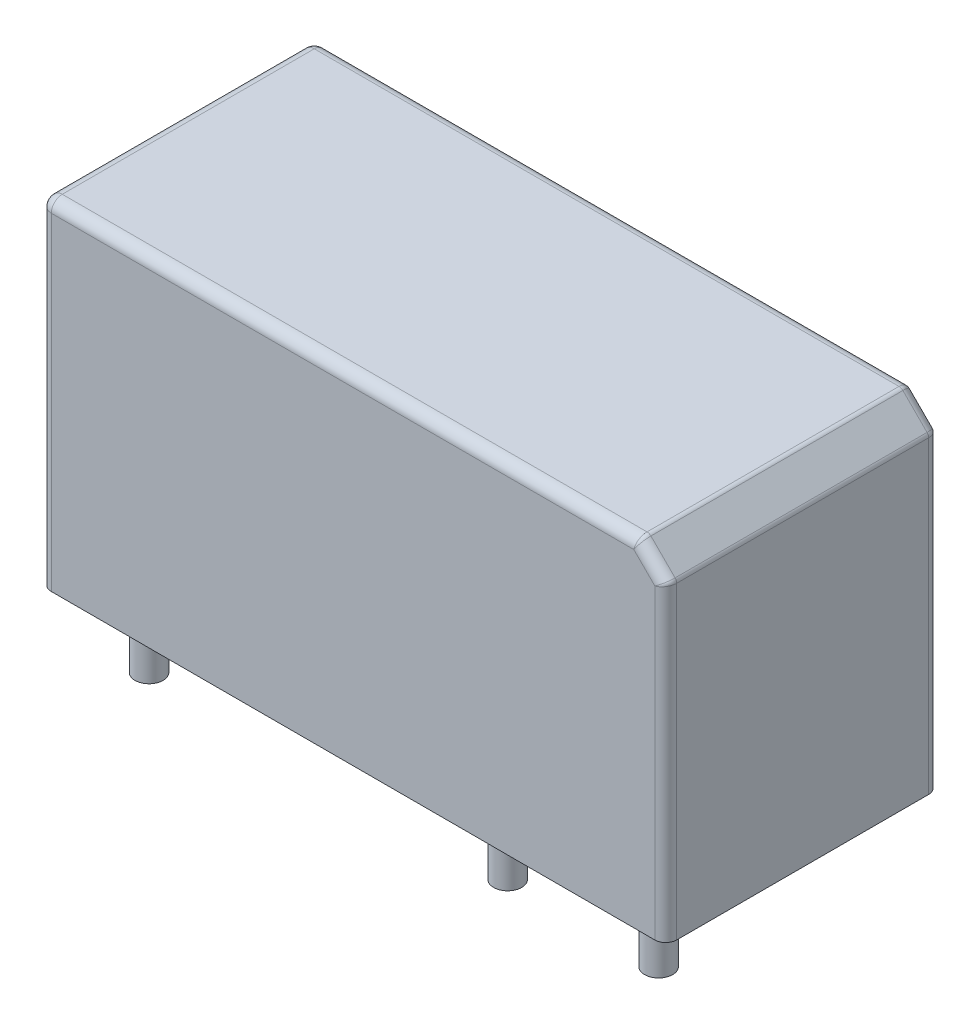
SolidWorks part; units mm, degrees
ref_plane "Front Plane" through (0, 0, 0) normal (0, 0, 1) x (1, 0, 0)
ref_plane "Top Plane" through (0, 0, 0) normal (0, 1, 0) x (1, 0, 0)
ref_plane "Right Plane" through (0, 0, 0) normal (1, 0, 0) x (0, 0, -1)
sketch "Sketch1" plane through (0, 0, 0) normal (0, 1, 0) x (1, 0, 0)
  line L0 (19.15, 2.52) -> (26.15, 2.52) construction
  line L1 (0, 0) -> (29, 0)
  line L2 (0, 0) -> (0, 12.7)
  line L3 (0, 12.7) -> (29, 12.7)
  line L4 (29, 0) -> (29, 12.7)
  line L5 (2.52, 2.52) -> (19.15, 2.52) construction
  line L6 (2.52, 10.02) -> (22.65, 10.02) construction
  line L7 (2.52, 10.02) -> (2.52, 2.52) construction
  circle A0 centre (2.52, 10.02) radius 0.65
  circle A1 centre (2.52, 2.52) radius 0.65
  circle A2 centre (19.15, 2.52) radius 0.65
  circle A3 centre (26.15, 2.52) radius 0.65
  circle A4 centre (22.65, 10.02) radius 0.65
  dimension "D2" = 1.3
  dimension "D1" = 29
  dimension "D3" = 2.52
  dimension "D4" = 22.65
  dimension "D5" = 7
  dimension "D6" = 3.5
  dimension "D8" = 12.7
extrude "Boss-Extrude1" add sketch "Sketch1" along normal blind 15.7 contours A1 | A0 | L1 L4 L3 L2 A4 A3 A2 A1 A0 | A4 | A3 | A2 region at (14.4982, 0, -6.3652) region at (2.52, 0, -10.02) region at (2.52, 0, -2.52) region at (19.15, 0, -2.52) region at (26.15, 0, -2.52) region at (22.65, 0, -10.02)
chamfer "Chamfer1" distance 1.27 angle 45 1 edges at (29, 15.7, -6.35)
fillet "Fillet1" radius 0.254 2 edges at (29, 14.43, -6.35) (27.73, 15.7, -6.35)
fillet "Fillet2" radius 0.508 13 edges at (13.8124, 15.7, -12.7) (27.722, 15.6807, -12.7) (28.365, 15.065, -12.7) (28.9807, 14.422, -12.7) (13.8124, 15.7, 0) (27.722, 15.6807, 0) (28.365, 15.065, 0) (28.9807, 14.422, 0) (0, 15.7, -6.35) (29, 7.1624, -12.7) (29, 7.1624, 0) (0, 7.85, -12.7) (0, 7.85, 0)
extrude "Boss-Extrude2" add sketch "Sketch1<3>" against normal blind 3.5 contours A1 | A0 | A4 | A2 | A3 region at (2.52, 0, -10.02) region at (2.52, 0, -2.52) region at (19.15, 0, -2.52) region at (26.15, 0, -2.52) region at (22.65, 0, -10.02)
sketch "Sketch1<3>" plane through (0, 0, 0) normal (0, 1, 0) x (1, 0, 0) same geometry as "Sketch1"
